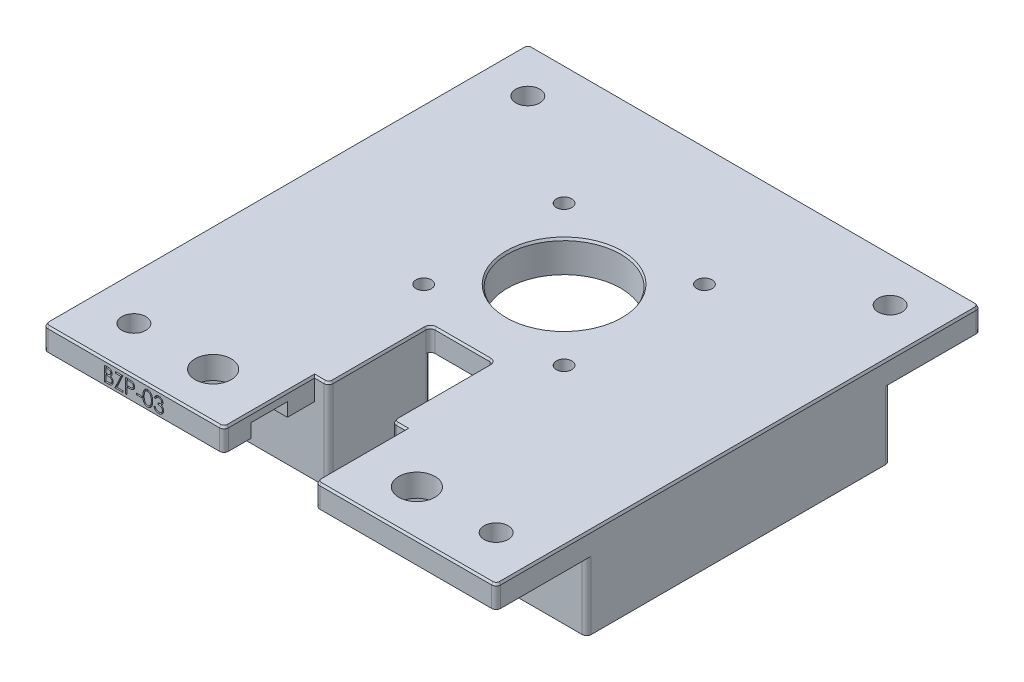
SolidWorks part; units mm, degrees
ref_plane "Front" through (0, 0, 0) normal (0, 0, 1) x (1, 0, 0)
ref_plane "Top" through (0, 0, 0) normal (0, 1, 0) x (1, 0, 0)
ref_plane "Right" through (0, 0, 0) normal (1, 0, 0) x (0, 0, -1)
sketch "Sketch2" plane through (0, 0, 0) normal (0, 1, 0) x (1, 0, 0)
  line L1 (0, 0) -> (100, 0)
  line L2 (0, 0) -> (0, 107)
  line L3 (0, 107) -> (100, 107)
  line L4 (100, 0) -> (100, 107)
  dimension "D1" = 107
  dimension "D2" = 100
extrude "Boss-Extrude1" add sketch "Sketch2" along normal blind 5
sketch "Sketch3" plane through (0, 5, 0) normal (0, 1, 0) x (1, 0, 0)
  line L0 (39.9, 0) -> (39.9, 20)
  line L1 (0, 0) -> (100, 0) construction
  line L2 (39.9, 20) -> (43, 20)
  line L3 (43, 20) -> (43, 42.5)
  line L4 (43, 42.5) -> (57, 42.5)
  line L5 (57, 42.5) -> (57, 20)
  line L6 (57, 20) -> (60.1, 20)
  line L7 (60.1, 20) -> (60.1, 0)
  line L8 (60.1, 0) -> (39.9, 0)
  line L9 (50, 107) -> (50, 65) construction
  line L10 (100, 107) -> (0, 107) construction
  line L11 (43, 42.5) -> (27.5, 42.5) construction
  line L12 (27.5, 87.5) -> (72.5, 87.5) construction
  line L13 (27.5, 87.5) -> (27.5, 42.5) construction
  line L14 (34.5, 49.5) -> (65.5, 49.5) construction
  line L15 (34.5, 49.5) -> (34.5, 80.5) construction
  line L16 (34.5, 80.5) -> (65.5, 80.5) construction
  line L17 (65.5, 49.5) -> (65.5, 80.5) construction
  line L18 (34.5, 49.5) -> (65.5, 80.5) construction
  line L19 (34.5, 80.5) -> (65.5, 49.5) construction
  line L20 (27.5, 42.5) -> (72.5, 42.5) construction
  line L21 (72.5, 87.5) -> (72.5, 42.5) construction
  line L22 (27.5, 87.5) -> (72.5, 42.5) construction
  line L23 (27.5, 42.5) -> (72.5, 87.5) construction
  line L24 (57, 42.5) -> (72.5, 42.5) construction
  line L25 (40, 10) -> (27.5, 10) construction
  line L26 (75, 47) -> (25, 47) construction
  line L27 (75, 47) -> (75, 83) construction
  line L28 (75, 83) -> (25, 83) construction
  line L29 (25, 47) -> (25, 83) construction
  line L30 (75, 47) -> (25, 83) construction
  line L31 (75, 83) -> (25, 47) construction
  line L32 (50, 65) -> (50, 10) construction
  line L33 (40, 0) -> (60, 0) construction
  line L34 (40, 0) -> (40, 20) construction
  line L35 (40, 20) -> (60, 20) construction
  line L36 (60, 0) -> (60, 20) construction
  line L37 (40, 0) -> (60, 20) construction
  line L38 (40, 20) -> (60, 0) construction
  circle A0 centre (50, 65) radius 12.5
  circle A1 centre (65.5, 49.5) radius 1.7
  circle A2 centre (34.5, 49.5) radius 1.7
  circle A3 centre (65.5, 80.5) radius 1.7
  circle A4 centre (34.5, 80.5) radius 1.7
  circle A5 centre (25, 83) radius 1.7 construction
  circle A6 centre (25, 47) radius 1.7 construction
  circle A7 centre (75, 47) radius 1.7 construction
  circle A8 centre (75, 83) radius 1.7 construction
  circle A9 centre (27.5, 10) radius 4
  circle A10 centre (72.5, 10) radius 4
  point P11 (50, 0)
  point P12 (50, 0)
  point P42 (50, 10)
  dimension "D4" = 25
  dimension "D6" = 3.4
  dimension "D10" = 3.4
  dimension "D12" = 8
  dimension "D2" = 14
  dimension "D3" = 20.2
  dimension "D5" = 31
  dimension "D7" = 42
  dimension "D8" = 50
  dimension "D9" = 36
  dimension "D11" = 45
  dimension "D13" = 20
  dimension "D14" = 12.5
  dimension "D15" = 20
extrude "Cut-Extrude1" cut sketch "Sketch3" against normal through all both and the other way through all
hole_wizard "M5 Clearance Hole1" positions "Sketch6" profile "Sketch5" hole size "M5" standard "ANSI Metric" end condition through all
sketch "Sketch6" plane through (0, 5, 0) normal (0, 1, 0) x (1, 0, 0)
  line L0 (0, 97) -> (100, 97) construction
  line L1 (0, 107) -> (0, 0) construction
  line L2 (100, 0) -> (100, 107) construction
  line L5 (10, 107) -> (10, 0) construction
  line L6 (100, 107) -> (0, 107) construction
  line L7 (0, 0) -> (39.9, 0) construction
  line L10 (90, 107) -> (90, 0) construction
  line L11 (60.1, 0) -> (100, 0) construction
  line L14 (0, 10) -> (100, 10) construction
  point P0 (10, 97)
  point P2 (10, 10)
  point P4 (90, 10)
  point P6 (90, 97)
  dimension "D1" = 10
  dimension "D2" = 10
  dimension "D3" = 10
  dimension "D4" = 10
sketch "Sketch5" plane through (10, 5, -97) normal (1, 0, 0) x (0, 0, 1)
  line L0 (0, 0) -> (0, 5)
  line L1 (0, 5) -> (2.65, 5)
  line L2 (2.65, 5) -> (2.65, 0)
  line L5 (2.65, 0) -> (0, 0)
  line L11 (0, -6.35) -> (0, 107.95) construction
  dimension "Thru Hole Dia." = 5.3
  dimension "Thru Hole Depth" = 5
fillet "Fillet1" radius 1 8 edges at (60.1, 2.5, 0) (39.9, 2.5, 0) (0, 2.5, -107) (100, 2.5, -107) (100, 2.5, 0) (0, 2.5, 0) (57, 2.5, -42.5) (43, 2.5, -42.5)
sketch "Sketch7" plane through (0, 0, 0) normal (0, -1, 0) x (1, 0, 0)
  line L0 (57, -20) -> (100, -20)
  line L1 (100, -1) -> (100, -106) construction
  line L2 (100, -20) -> (100, -87)
  line L3 (100, -87) -> (84, -87)
  line L4 (84, -87) -> (84, -82)
  line L5 (84, -82) -> (95, -82)
  line L6 (95, -82) -> (95, -25)
  line L7 (95, -25) -> (57, -25) construction
  line L8 (57, -25) -> (57, -20)
  line L9 (61.1, 0) -> (99, 0) construction
  line L10 (57, -20) -> (57, -41.5) construction
  line L11 (99, -107) -> (1, -107) construction
  line L12 (50, -107) -> (50, -46.1063) construction
  line L13 (43, -25) -> (43, -20)
  line L14 (5, -25) -> (43, -25) construction
  line L15 (5, -82) -> (5, -25)
  line L16 (16, -82) -> (5, -82)
  line L17 (16, -87) -> (16, -82)
  line L18 (0, -87) -> (16, -87)
  line L19 (0, -20) -> (0, -87)
  line L20 (43, -20) -> (0, -20)
  line L21 (57, -25) -> (57, -42.5)
  line L23 (57, -42.5) -> (62, -42.5)
  line L25 (62, -42.5) -> (62, -25)
  line L26 (62, -25) -> (95, -25)
  line L27 (38, -25) -> (5, -25)
  line L28 (38, -42.5) -> (38, -25)
  line L29 (43, -25) -> (43, -42.5)
  line L31 (43, -42.5) -> (38, -42.5)
  line L32 (56, -42.5) -> (44, -42.5) construction
  dimension "D1" = 20
  dimension "D2" = 20
  dimension "D3" = 16
  dimension "D4" = 5
  dimension "D5" = 5
extrude "Boss-Extrude2" add sketch "Sketch7" along normal blind 15
fillet "Fillet3" radius 3 6 edges at (5, -7.5, -82) (95, -7.5, -82) (5, -7.5, -25) (38, -7.5, -25) (95, -7.5, -25) (62, -7.5, -25)
fillet "Fillet4" radius 1 14 edges at (100, -7.5, -87) (100, -7.5, -20) (43, -5, -20) (57, -5, -20) (84, -7.5, -87) (84, -7.5, -82) (0, -7.5, -20) (0, -7.5, -87) (16, -7.5, -87) (16, -7.5, -82) (38, -7.5, -42.5) (62, -7.5, -42.5) (57, -7.5, -42.5) (43, -7.5, -42.5)
ref_plane "Plane1" through (0, 0, -10) normal (0, 0, 1) x (1, 0, 0)
sketch "Sketch9" plane through (0, 0, -10) normal (0, 0, 1) x (1, 0, 0)
  line L0 (39.9, 0) -> (39.9, 3)
  line L2 (39.9, 0) -> (39.9, 5) construction
  line L3 (39.9, 3) -> (36.9, 0)
  line L4 (36.9, 0) -> (39.9, 0)
  line L5 (60.1, 0) -> (63.1, 0)
  line L6 (99, 0) -> (60.1, 0) construction
  line L7 (63.1, 0) -> (60.1, 3)
  line L8 (60.1, 0) -> (60.1, 5) construction
  line L9 (60.1, 3) -> (60.1, 0)
  dimension "D1" = 45
  dimension "D2" = 3
extrude "Cut-Extrude2" cut sketch "Sketch9" against normal blind 4 and the other way blind 4
sketch "Sketch12" plane through (0, 0, 0) normal (0, -1, 0) x (1, 0, 0)
  line L0 (34.5, -85.5) -> (65.5, -85.5)
  line L1 (70.5, -80.5) -> (70.5, -49.5)
  line L2 (65.5, -44.5) -> (34.5, -44.5)
  line L3 (29.5, -49.5) -> (29.5, -80.5)
  circle A0 centre (34.5, -80.5) radius 5 construction
  circle A1 centre (65.5, -80.5) radius 5 construction
  circle A2 centre (65.5, -49.5) radius 5 construction
  circle A3 centre (34.5, -49.5) radius 5 construction
  arc A4 (65.5, -85.5) -> (70.5, -80.5) centre (65.5, -80.5) ccw
  arc A5 (34.5, -85.5) -> (29.5, -80.5) centre (34.5, -80.5) cw
  arc A6 (65.5, -44.5) -> (70.5, -49.5) centre (65.5, -49.5) cw
  arc A7 (29.5, -49.5) -> (34.5, -44.5) centre (34.5, -49.5) cw
  circle A8 centre (50, -65) radius 12.5 construction
  circle A9 centre (50, -65) radius 12.5
  circle A10 centre (34.5, -49.5) radius 1.7 construction
  circle A11 centre (65.5, -49.5) radius 1.7 construction
  circle A12 centre (65.5, -80.5) radius 1.7 construction
  circle A13 centre (34.5, -80.5) radius 1.7 construction
  circle A14 centre (34.5, -49.5) radius 1.7
  circle A15 centre (65.5, -49.5) radius 1.7
  circle A16 centre (65.5, -80.5) radius 1.7
  circle A17 centre (34.5, -80.5) radius 1.7
  dimension "D1" = 10
extrude "Boss-Extrude3" add sketch "Sketch12" along normal blind 2
chamfer "Chamfer2" distance 0.5 angle 45 8 edges at (50, 0, -85.5) (69.0355, 0, -84.0355) (30.9645, 0, -84.0355) (70.5, 0, -65) (29.5, 0, -65) (69.0355, 0, -45.9645) (30.9645, 0, -45.9645) (50, 0, -44.5)
sketch "Sketch10" plane through (0, 5, 0) normal (0, 0, -1) x (1, 0, 0)
  line L0 (0, 4.4) -> (39.9, 4.4) construction
  line L2 (1, 5) -> (38.9, 5) construction
  line L5 (39.9, 0) -> (39.9, 5) construction
  text T0 "BZP-03" font "Century Gothic" height in points 12
  dimension "D1" = 0.6
extrude "Part Num" cut sketch "Sketch10" along normal blind 0.4
chamfer "Printability Chamfer" distance 0.5 angle 30 23 edges at (59.05, 5, -20) (57.2929, 5, -20.2929) (57, 5, -31.25) (56.7071, 5, -42.2071) (50, 5, -42.5) (43.2929, 5, -42.2071) (43, 5, -31.25) (42.7071, 5, -20.2929) (40.95, 5, -20) (50, 5, -77.5) (60.1, 5, -10.5) (60.3929, 5, -0.2929) (80.05, 5, 0) (99.7071, 5, -0.2929) (100, 5, -53.5) (99.7071, 5, -106.7071) (50, 5, -107) (0.2929, 5, -106.7071) (0, 5, -53.5) (39.9, 5, -10.5) (0.2929, 5, -0.2929) (39.6071, 5, -0.2929) (19.95, 5, 0) first distance on face at (72.3667, -3.3333, -20) first distance on face at (57.3964, -5, -20.3964) first distance on face at (57, -4, -33.3) first distance on face at (56.6036, 2.5, -42.1036) first distance on face at (50, 2.5, -42.5) first distance on face at (43.3964, 2.5, -42.1036) first distance on face at (43, -4, -33.3) first distance on face at (42.6036, -5, -20.3964) first distance on face at (27.6333, -3.3333, -20) first distance on face at (50, 5, -77.5) first distance on face at (60.1, 2, -10.25) first distance on face at (60.4964, 2.5, -0.3964) first distance on face at (80.05, 2.5, 0) first distance on face at (99.6036, 2.5, -0.3964) first distance on face at (100, -2.5, -53.5) first distance on face at (99.6036, 2.5, -106.6036) first distance on face at (50, 2.5, -107) first distance on face at (0.3964, 2.5, -106.6036) first distance on face at (0, -2.5, -53.5) first distance on face at (39.9, 2, -10.25) first distance on face at (0.3964, 2.5, -0.3964) first distance on face at (39.5036, 2.5, -0.3964) first distance on face at (16.7139, 2.1875, 0)
equation "\"D5@Sketch7\"=\"D4@Sketch7\""
